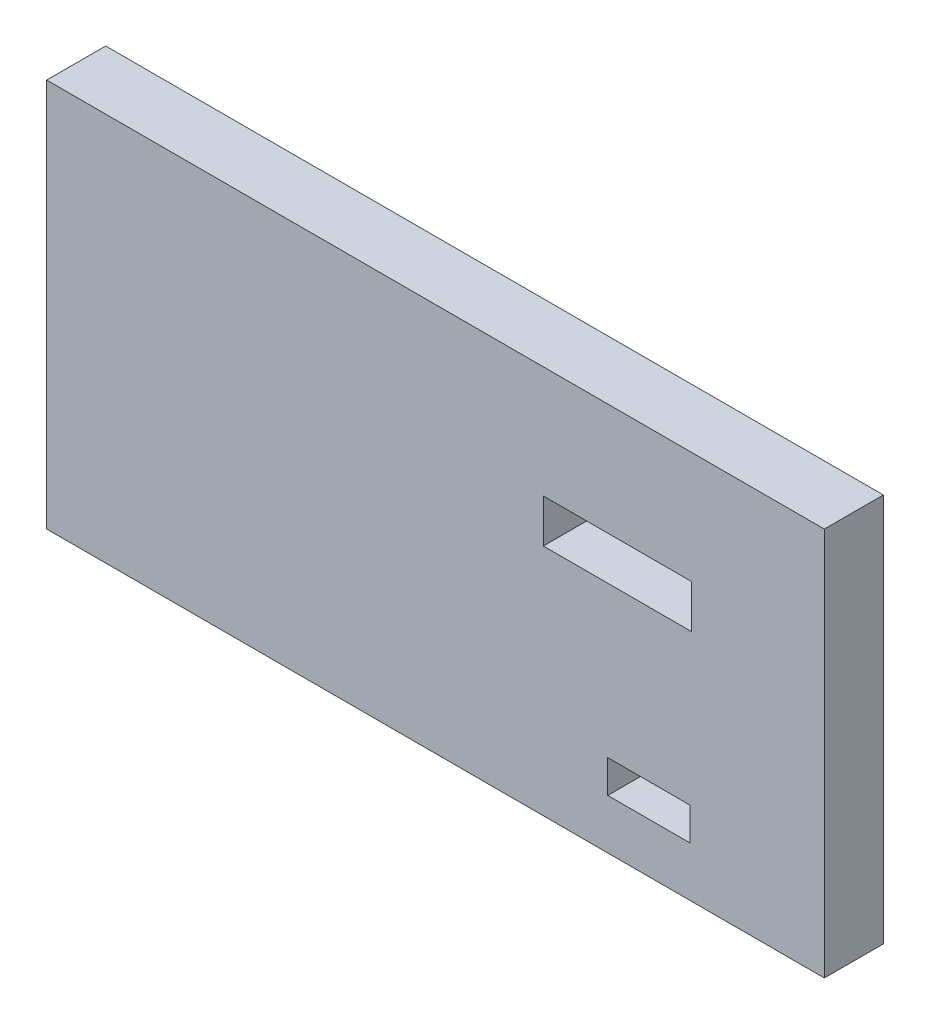
SolidWorks part; units mm, degrees
ref_plane "Front Plane" through (0, 0, 0) normal (0, 0, 1) x (1, 0, 0)
ref_plane "Top Plane" through (0, 0, 0) normal (0, 1, 0) x (1, 0, 0)
ref_plane "Right Plane" through (0, 0, 0) normal (1, 0, 0) x (0, 0, -1)
sketch "Sketch1" plane through (0, 0, 0) normal (0, 0, 1) x (1, 0, 0)
  line L1 (0, 0) -> (131.7823, 0)
  line L2 (0, 0) -> (0, 65.8912)
  line L3 (0, 65.8912) -> (131.7823, 65.8912)
  line L4 (131.7823, 0) -> (131.7823, 65.8912)
  line L5 (84.1666, 46.9356) -> (109.2895, 46.9356)
  line L6 (84.1666, 46.9356) -> (84.1666, 39.5891)
  line L7 (84.1666, 39.5891) -> (109.2895, 39.5891)
  line L8 (109.2895, 46.9356) -> (109.2895, 39.5891)
extrude "Boss-Extrude1" add sketch "Sketch1" along normal blind 10
sketch "Sketch2" plane through (0, 0, 10) normal (0, 0, 1) x (1, 0, 0)
  circle A0 centre (30.9238, 22.9153) radius 10.8112
sketch "Sketch3" plane through (0, 0, 10) normal (0, 0, 1) x (1, 0, 0)
  line L1 (95.0793, 13.9905) -> (108.9924, 13.9905)
  line L2 (95.0793, 13.9905) -> (95.0793, 8.4416)
  line L3 (95.0793, 8.4416) -> (108.9924, 8.4416)
  line L4 (108.9924, 13.9905) -> (108.9924, 8.4416)
extrude "Cut-Extrude1" cut sketch "Sketch3" against normal blind 10
